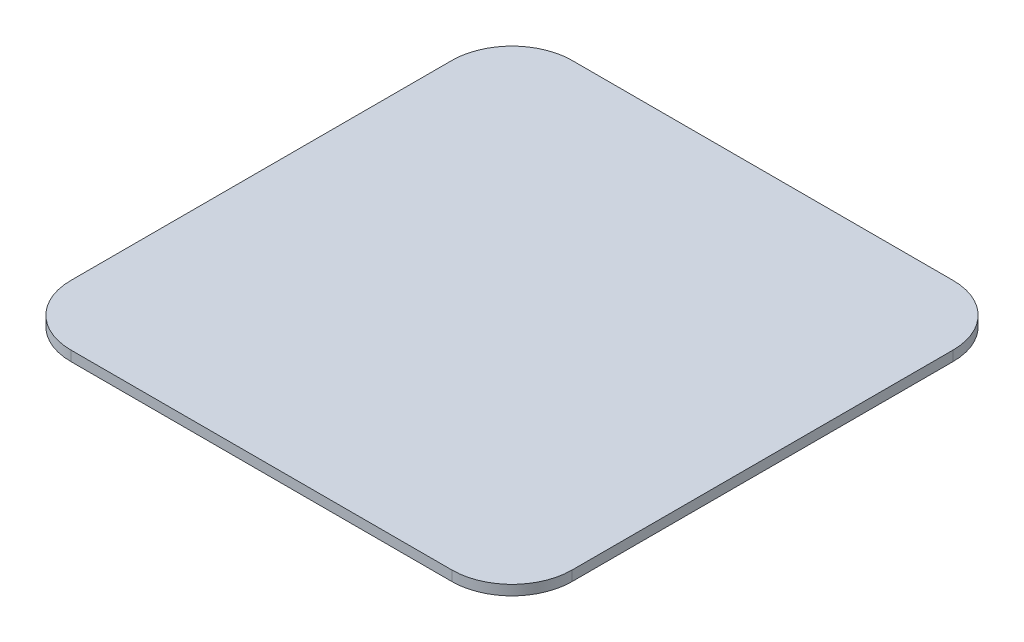
SolidWorks part; units mm, degrees
ref_plane "Front Plane" through (0, 0, 0) normal (0, 0, 1) x (1, 0, 0)
ref_plane "Top Plane" through (0, 0, 0) normal (0, 1, 0) x (1, 0, 0)
ref_plane "Right Plane" through (0, 0, 0) normal (1, 0, 0) x (0, 0, -1)
sketch "Sketch1" plane through (0, 0, 0) normal (0, 1, 0) x (1, 0, 0)
  line L1 (-190, -250) -> (190, -250)
  line L2 (-250, -190) -> (-250, 190)
  line L3 (-190, 250) -> (190, 250)
  line L4 (250, -190) -> (250, 190)
  line L5 (-250, -250) -> (250, 250) construction
  line L6 (-250, 250) -> (250, -250) construction
  arc A0 (250, 190) -> (190, 250) centre (190, 190) ccw
  arc A1 (250, -190) -> (190, -250) centre (190, -190) cw
  arc A2 (-190, -250) -> (-250, -190) centre (-190, -190) cw
  arc A3 (-250, 190) -> (-190, 250) centre (-190, 190) cw
  point P0 (0, 0)
  dimension "D3" = 60
  dimension "D1" = 500
  dimension "D2" = 500
extrude "Boss-Extrude1" add sketch "Sketch1" along normal blind 10
